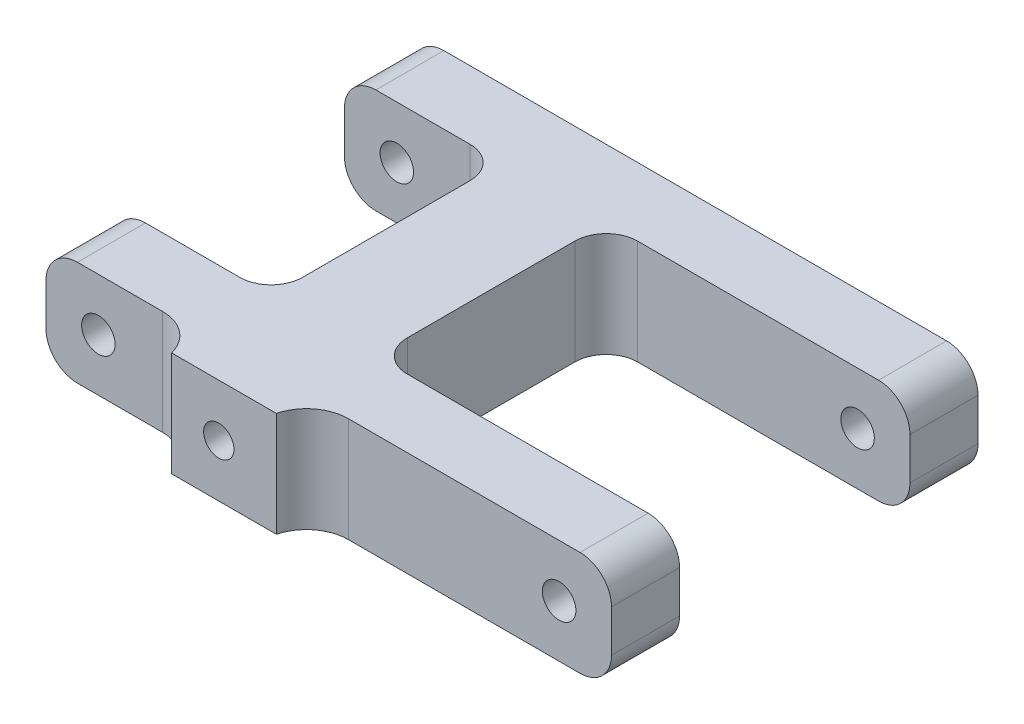
SolidWorks part; units mm, degrees
ref_plane "Front" through (0, 0, 0) normal (0, 0, 1) x (1, 0, 0)
ref_plane "Top" through (0, 0, 0) normal (0, 1, 0) x (1, 0, 0)
ref_plane "Right" through (0, 0, 0) normal (1, 0, 0) x (0, 0, -1)
sketch "Sketch1" plane through (0, 0, 0) normal (0, 1, 0) x (1, 0, 0)
  line L1 (0, 0) -> (54, 0)
  line L2 (0, 0) -> (0, -35)
  line L3 (0, -35) -> (54, -35)
  line L4 (54, 0) -> (54, -35)
  dimension "D1" = 35
  dimension "D2" = 54
extrude "Boss-Extrude1" add sketch "Sketch1" along normal blind 10
sketch "Sketch2" plane through (54, 0, 0) normal (1, 0, 0) x (0, 0, -1)
  line L0 (-35, 10) -> (0, 10) construction
  line L1 (-28.5, 10) -> (-6.5, 10)
  line L2 (-28.5, 10) -> (-28.5, 0)
  line L3 (-28.5, 0) -> (-6.5, 0)
  line L4 (-6.5, 10) -> (-6.5, 0)
  line L5 (-35, 0) -> (0, 0) construction
  line L6 (-35, 10) -> (-35, 0) construction
  line L7 (0, 10) -> (0, 0) construction
  dimension "D1" = 6.5
  dimension "D2" = 6.5
extrude "Cut-Extrude1" cut sketch "Sketch2" against normal blind 29
sketch "Sketch3" plane through (0, 0, 0) normal (-1, 0, 0) x (0, 0, 1)
  line L0 (0, 10) -> (35, 10) construction
  line L1 (6.5, 10) -> (28.5, 10)
  line L2 (6.5, 10) -> (6.5, 0)
  line L3 (6.5, 0) -> (28.5, 0)
  line L4 (28.5, 10) -> (28.5, 0)
  line L5 (0, 0) -> (35, 0) construction
  line L6 (35, 10) -> (35, 0) construction
  line L7 (0, 10) -> (0, 0) construction
  dimension "D1" = 6.5
  dimension "D2" = 6.5
extrude "Cut-Extrude2" cut sketch "Sketch3" against normal blind 15
sketch "Sketch5" plane through (0, 0, 35) normal (0, 0, 1) x (1, 0, 0)
  line L0 (0, 10) -> (54, 10) construction
  line L1 (0, 10) -> (0, 0) construction
  circle A0 centre (5, 5) radius 1.6
  circle A1 centre (49, 5) radius 1.6
  dimension "D1" = 3.2
  dimension "D2" = 5
  dimension "D3" = 5
  dimension "D4" = 2
extrude "Cut-Extrude4" cut sketch "Sketch5" against normal through all
fillet "Fillet1" radius 3 8 edges at (0, 0, 31.75) (0, 10, 31.75) (0, 0, 3.25) (0, 10, 3.25) (54, 10, 3.25) (54, 0, 3.25) (54, 0, 31.75) (54, 10, 31.75)
fillet "Fillet2" radius 3 4 edges at (25, 5, 28.5) (25, 5, 6.5) (15, 5, 28.5) (15, 5, 6.5)
sketch "Sketch8" plane through (0, 0, 35) normal (0, 0, 1) x (1, 0, 0)
  line L0 (3, 10) -> (51, 10) construction
  line L1 (15, 10) -> (25, 10)
  line L2 (15, 10) -> (15, 0)
  line L3 (15, 0) -> (25, 0)
  line L4 (25, 10) -> (25, 0)
  line L5 (3, 0) -> (51, 0) construction
  line L6 (54, 7) -> (54, 3) construction
  line L7 (0, 7) -> (0, 3) construction
  dimension "D1" = 29
  dimension "D2" = 15
extrude "Boss-Extrude2" add sketch "Sketch8" along normal blind 3
sketch "Sketch6" plane through (0, 0, 35) normal (0, 0, 1) x (1, 0, 0)
  line L0 (3, 10) -> (15, 10) construction
  line L2 (54, 7) -> (54, 3) construction
  circle A0 centre (19.5, 5) radius 1.45
  dimension "D1" = 2.9
  dimension "D2" = 5
  dimension "D3" = 34.5
extrude "Cut-Extrude5" cut sketch "Sketch6" against normal blind 15 and the other way blind 4
fillet "Fillet3" radius 4 2 edges at (25, 5, 35) (15, 5, 35)
